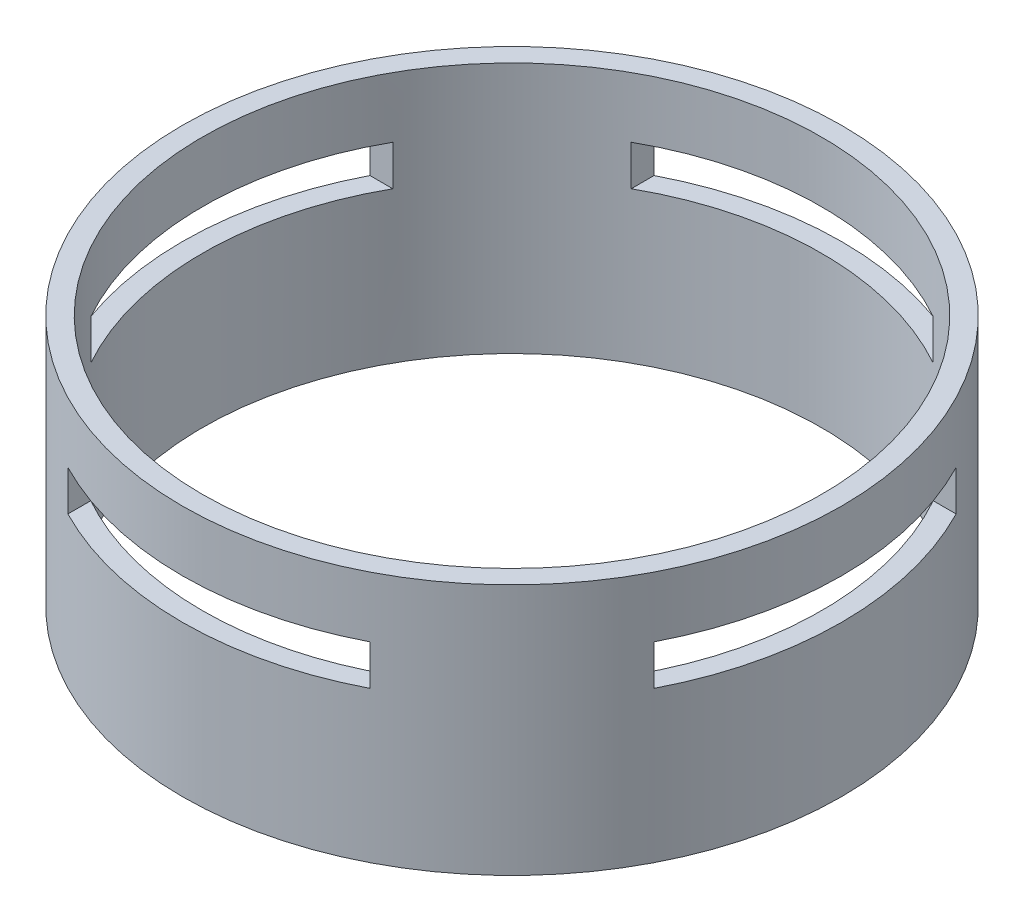
SolidWorks part; units mm, degrees
material "ABS"
ref_plane "Plan de face" through (0, 0, 0) normal (0, 0, 1) x (1, 0, 0)
ref_plane "Plan de dessus" through (0, 0, 0) normal (0, 1, 0) x (1, 0, 0)
ref_plane "Plan de droite" through (0, 0, 0) normal (1, 0, 0) x (0, 0, -1)
sketch "Esquisse1" plane through (0, 0, 0) normal (0, 1, 0) x (1, 0, 0)
  circle A0 centre (0, 0) radius 32.75
  circle A1 centre (0, 0) radius 30.75
  dimension "D1" = 65.5
  dimension "D2" = 2
extrude "Boss.-Extru.1" add sketch "Esquisse1" along normal blind 25
sketch "Esquisse2" plane through (0, 0, 0) normal (0, 0, 1) x (1, 0, 0)
  line L0 (0, 0) -> (0, 25) construction
  line L1 (-32.75, 0) -> (32.75, 0) construction
  line L2 (-15, 19) -> (15, 19)
  line L3 (-15, 19) -> (-15, 15)
  line L4 (-15, 15) -> (15, 15)
  line L5 (30.75, 25) -> (-30.75, 25) construction
  line L6 (15, 19) -> (15, 15)
  point P9 (0, 15)
  dimension "D1" = 4
  dimension "D2" = 30
  dimension "D3" = 15
extrude "Enlèv. mat.-Extru.1" cut sketch "Esquisse2" against normal through all
pattern_circular "Répétition circulaire1" count 4 every 90 about axis through (0, 25, 0) along (0, -1, 0) of "Enlèv. mat.-Extru.1"
